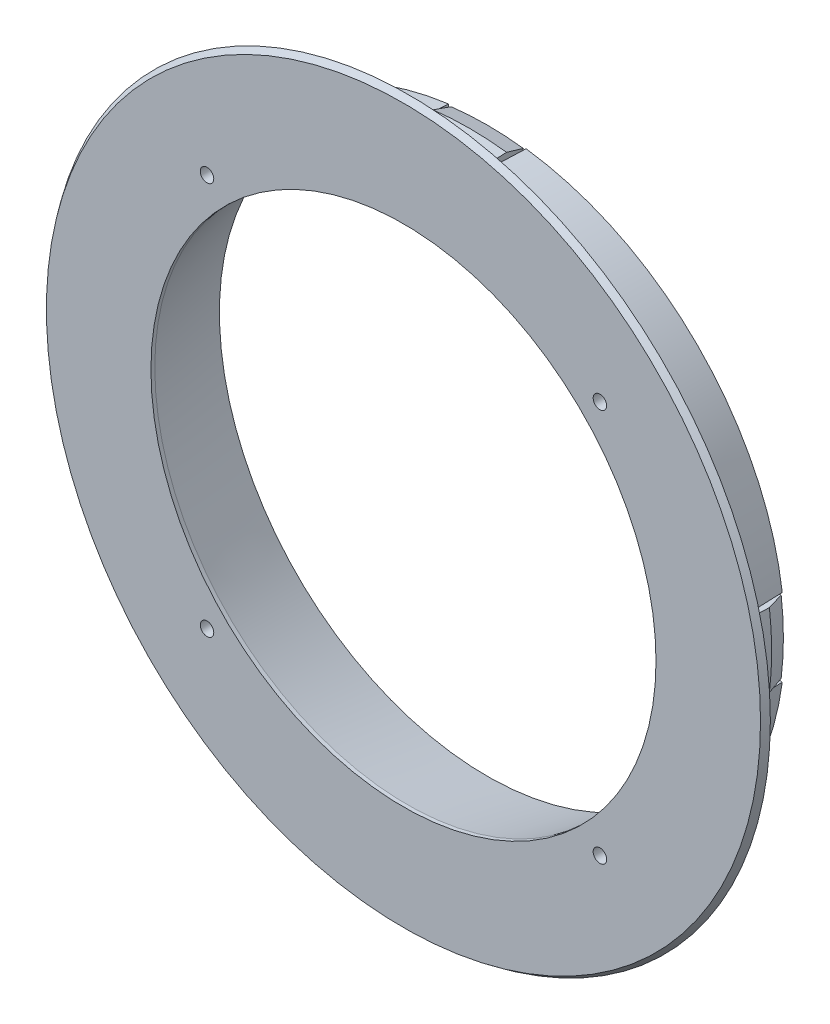
SolidWorks part; units mm, degrees
ref_plane "Спереди" through (0, 0, 0) normal (0, 0, 1) x (1, 0, 0)
ref_plane "Сверху" through (0, 0, 0) normal (0, 1, 0) x (1, 0, 0)
ref_plane "Справа" through (0, 0, 0) normal (1, 0, 0) x (0, 0, -1)
sketch "Main_profile" plane through (0, 0, 0) normal (0, 1, 0) x (1, 0, 0)
  line L0 (0, -21.597) -> (0, 33.5055) construction
  line L1 (-74.1598, 0) -> (-62.45, 0)
  line L2 (-52.45, 0.8) -> (-55.6294, 17.4)
  line L3 (-55.6294, 17.4) -> (-61.8, 17.4)
  line L4 (-61.8, 17.4) -> (-62.5, 1.2)
  line L5 (-62.5, 1.2) -> (-75, 1.2)
  line L6 (-75, 1.2) -> (-74.1598, 0)
  line L7 (-62.45, 0) -> (-62.45, 0.8)
  line L8 (-62.45, 0.8) -> (-52.45, 0.8)
  line L9 (-62.45, 0) -> (-52.45, 0)
  line L10 (-52.45, 0) -> (-52.45, 0.8)
  line L13 (-61.5069, 17.4) -> (-62.7, 13.7731)
  line L14 (-62.7, 13.7731) -> (-62.3072, 5.6622)
  line L15 (-61.5069, 17.4) -> (-60.3334, 17.4)
  line L16 (-60.3334, 17.4) -> (-60.3334, 5.0548)
  line L17 (-60.3334, 5.0548) -> (-59.9334, 5.0548)
  line L18 (-59.9334, 5.0548) -> (-59.3334, 17.4)
  line L19 (-60.3334, 5.0548) -> (-62.3334, 5.0548)
  point P4 (0, 0)
  point P14 (-61.5069, 17.4)
  dimension "D1" = 123.6
  dimension "D2" = 125
  dimension "D3" = 16.2
  dimension "D4" = 150
  dimension "D5" = 35
  dimension "D6" = 1.2
  dimension "D7" = 124.9
  dimension "D8" = 0.8
  dimension "D9" = 10
  dimension "D11" = 0.4
  dimension "D12" = 0.2
  dimension "D13" = 2
  dimension "D14" = 1
revolve "Main_body" add sketch "Main_profile" angle 360 about L0 region at (-58.6216, 0, -6.7719) region at (-57.45, 0, -0.4) region at (-61.2033, 0, -10.8673) region at (-59.962, 0, -12.1092) region at (-61.7171, 0, -17.0581)
revolve "clamp_cutoff" cut sketch "Эскиз1<8>" angle 15 mid plane about L0 region at (-61.2033, 0, -10.8673) region at (-59.962, 0, -12.1092) region at (-61.7171, 0, -17.0581)
sketch "Эскиз1<8>" plane through (0, 0, 0) normal (0, 1, 0) x (1, 0, 0) same geometry as "Main_profile"
revolve "Clamp_body" add sketch "Эскиз1<10>" angle 14 mid plane about L0 region at (-61.2033, 0, -10.8673) region at (-62.2838, 0, -11.9366)
sketch "Эскиз1<10>" plane through (0, 0, 0) normal (0, 1, 0) x (1, 0, 0) same geometry as "Main_profile"
pattern_circular "Clamp_array" count 4 over 360 about axis through (0, 0, -17.4) along (0, 0, 1) of "clamp_cutoff", "Clamp_body"
ref_plane "45" through (0, 0, 0) normal (0.7071, 0.7071, 0) x (0, 0, -1)
sketch "Hole_profile" plane through (0, 0, 0) normal (0.7071, 0.7071, 0) x (0, 0, -1)
  line L0 (17.4, 55.6294) -> (0.8, 52.45)
  line L1 (0.8, -52.45) -> (17.4, -55.6294)
  line L2 (0.8, -52.45) -> (17.4, -55.6294)
  line L3 (17.4, 55.6294) -> (0.8, 52.45)
  line L4 (1.2, 62.5) -> (17.4, 61.8)
  line L5 (17.4, -61.8) -> (1.2, -62.5)
  line L6 (17.4, -61.8) -> (1.2, -62.5)
  line L7 (1.2, 62.5) -> (17.4, 61.8)
  line L8 (17.4, 61.8) -> (17.4, 55.6294)
  line L9 (17.4, -55.6294) -> (17.4, -61.8)
  line L10 (17.4, -55.6294) -> (17.4, -61.8)
  line L11 (17.4, 61.8) -> (17.4, 55.6294)
  line L15 (0.8, -62.45) -> (0.8, -52.45)
  line L16 (0, -74.1598) -> (0, -52.45)
  line L17 (0, 52.45) -> (0, 74.1598)
  line L18 (0, 52.45) -> (0, 74.1598)
  line L19 (0, -74.1598) -> (0, -52.45)
  line L22 (0, -52.45) -> (0.8, -62.45)
  line L24 (-2.269, 57.7) -> (9.3566, 57.7) construction
  line L25 (-21.597, 0) -> (33.5055, 0) construction
  line L26 (0, 59.1) -> (13.4412, 58.6)
  line L27 (13.4412, 58.6) -> (15, 57.7)
  line L28 (15, 57.7) -> (0, 57.7)
  line L29 (0, 57.7) -> (0, 59.1)
  dimension "D1" = 57.7
  dimension "D2" = 2.8
  dimension "D3" = 15
  dimension "D4" = 1.8
  dimension "D5" = 30
revolve "Hole" cut sketch "Hole_profile" angle 360 about L24 region at (-41.2043, 41.2043, -6.569)
pattern_circular "Holes_array" count 4 over 360 about axis through (0, 0, 0) along (0, 0, 1) of "Hole"
